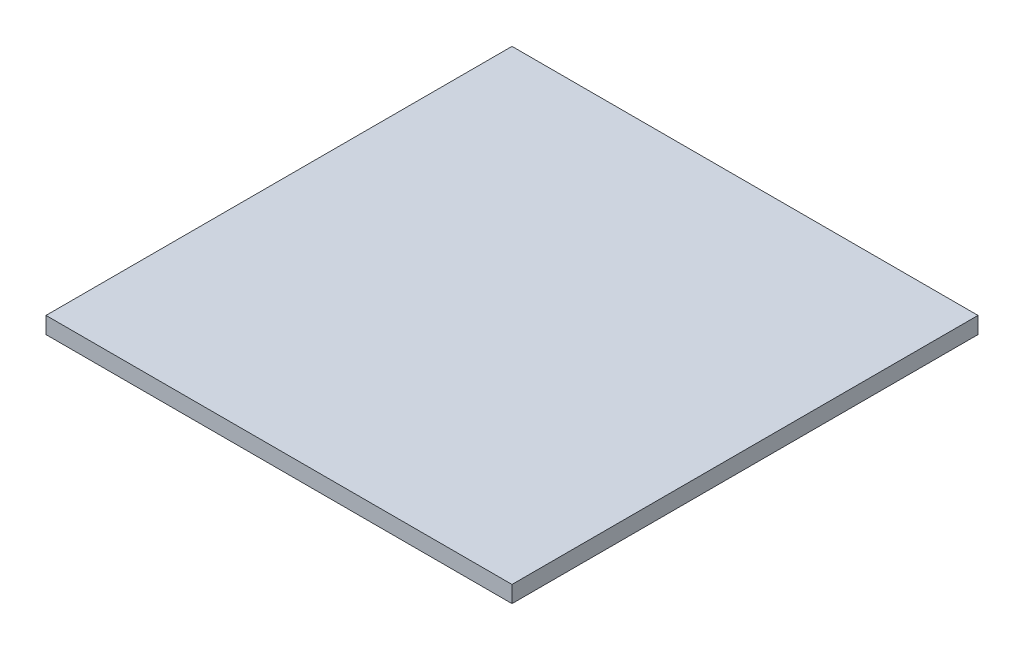
SolidWorks part; units mm, degrees
ref_plane "Front Plane" through (0, 0, 0) normal (0, 0, 1) x (1, 0, 0)
ref_plane "Top Plane" through (0, 0, 0) normal (0, 1, 0) x (1, 0, 0)
ref_plane "Right Plane" through (0, 0, 0) normal (1, 0, 0) x (0, 0, -1)
sketch "Sketch1" plane through (0, 0, 0) normal (0, 1, 0) x (1, 0, 0)
  line L1 (-70, 70) -> (70, 70)
  line L2 (-70, 70) -> (-70, -70)
  line L3 (-70, -70) -> (70, -70)
  line L4 (70, 70) -> (70, -70)
  line L5 (-70, 70) -> (70, -70) construction
  line L6 (-70, -70) -> (70, 70) construction
  point P0 (0, 0)
  dimension "D1" = 140
  dimension "D2" = 140
extrude "Boss-Extrude1" add sketch "Sketch1" along normal blind 5
